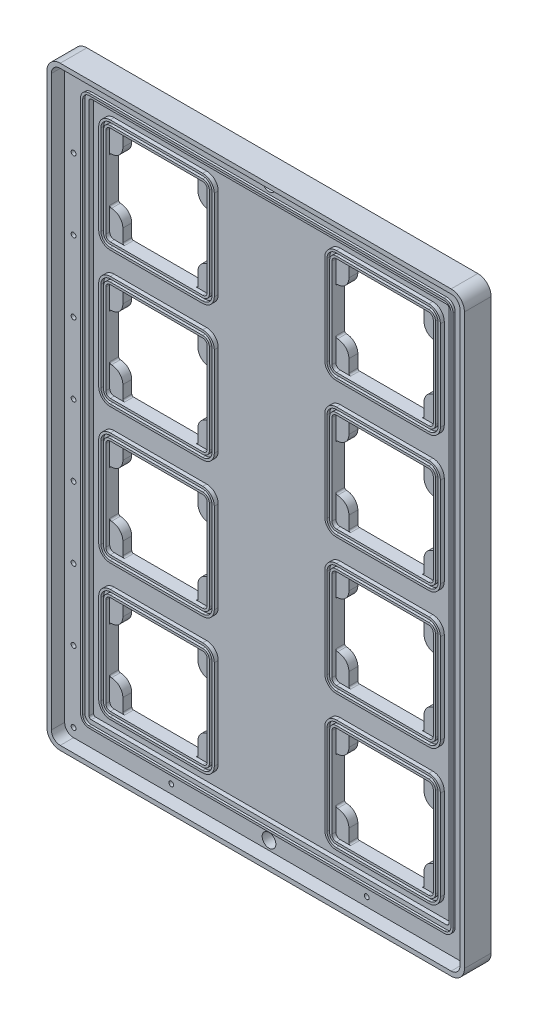
SolidWorks part; units mm, degrees
ref_plane "Front Plane" through (0, 0, 0) normal (0, 0, 1) x (1, 0, 0)
ref_plane "Top Plane" through (0, 0, 0) normal (0, 1, 0) x (1, 0, 0)
ref_plane "Right Plane" through (0, 0, 0) normal (1, 0, 0) x (0, 0, -1)
sketch "Sketch1" plane through (0, 0, 0) normal (0, 0, 1) x (1, 0, 0)
  line L1 (0, 0) -> (292.1, 0)
  line L2 (0, 0) -> (0, 419.1)
  line L3 (0, 419.1) -> (292.1, 419.1)
  line L4 (292.1, 0) -> (292.1, 419.1)
  dimension "D1" = 419.1
  dimension "D2" = 292.1
extrude "Boss-Extrude1" add sketch "Sketch1" along normal blind 9.525
sketch "Sketch4" plane through (0, 0, 9.525) normal (0, 0, 1) x (1, 0, 0)
  line L3 (0, 419.1) -> (0, 0) construction
  line L4 (6.35, 412.75) -> (285.75, 412.75) construction
  line L5 (6.35, 412.75) -> (6.35, 6.35) construction
  line L6 (6.35, 6.35) -> (285.75, 6.35) construction
  line L7 (285.75, 412.75) -> (285.75, 6.35) construction
  line L8 (292.1, 419.1) -> (0, 419.1) construction
  line L9 (292.1, 0) -> (292.1, 419.1) construction
  line L10 (0, 0) -> (292.1, 0) construction
  circle A0 centre (6.35, 6.35) radius 1.7272
  circle A1 centre (6.35, 412.75) radius 1.7272
  circle A2 centre (285.75, 412.75) radius 1.7272
  circle A3 centre (285.75, 6.35) radius 1.7272
  dimension "D5" = 3.4544
  dimension "D1" = 6.35
  dimension "D2" = 6.35
  dimension "D3" = 6.35
  dimension "D4" = 6.35
extrude "Cut-Extrude1" cut sketch "Sketch4" against normal blind 6.985
pattern_linear "LPattern2" count 8 spacing 50.8 along (0, -1, 0) of "Cut-Extrude1"
pattern_linear "LPattern3" count 4 spacing 69.85 along (-1, 0, 0) of "Cut-Extrude1"
sketch "Sketch5" plane through (0, 0, 9.525) normal (0, 0, 1) x (1, 0, 0)
  line L0 (0, 419.1) -> (0, 0) construction
  line L1 (19.05, 406.4) -> (273.05, 406.4) construction
  line L2 (12.7, 400.05) -> (12.7, 19.05) construction
  line L3 (19.05, 12.7) -> (273.05, 12.7) construction
  line L4 (279.4, 400.05) -> (279.4, 19.05) construction
  line L5 (292.1, 419.1) -> (0, 419.1) construction
  line L6 (292.1, 0) -> (292.1, 419.1) construction
  line L7 (0, 0) -> (292.1, 0) construction
  line L8 (19.05, 14.732) -> (273.05, 14.732) construction
  line L9 (14.732, 400.05) -> (14.732, 19.05) construction
  line L10 (19.05, 404.368) -> (273.05, 404.368) construction
  line L11 (277.368, 400.05) -> (277.368, 19.05) construction
  line L12 (12.954, 400.05) -> (12.954, 19.05)
  line L13 (19.05, 406.146) -> (273.05, 406.146)
  line L14 (279.146, 400.05) -> (279.146, 19.05)
  line L15 (19.05, 12.954) -> (273.05, 12.954)
  line L16 (277.622, 400.05) -> (277.622, 19.05)
  line L17 (19.05, 404.622) -> (273.05, 404.622)
  line L18 (14.478, 400.05) -> (14.478, 19.05)
  line L19 (19.05, 14.478) -> (273.05, 14.478)
  arc A0 (273.05, 12.7) -> (279.4, 19.05) centre (273.05, 19.05) ccw construction
  arc A1 (12.7, 19.05) -> (19.05, 12.7) centre (19.05, 19.05) ccw construction
  arc A2 (273.05, 406.4) -> (279.4, 400.05) centre (273.05, 400.05) cw construction
  arc A3 (19.05, 406.4) -> (12.7, 400.05) centre (19.05, 400.05) ccw construction
  arc A4 (14.732, 19.05) -> (19.05, 14.732) centre (19.05, 19.05) ccw construction
  arc A5 (19.05, 404.368) -> (14.732, 400.05) centre (19.05, 400.05) ccw construction
  arc A6 (273.05, 404.368) -> (277.368, 400.05) centre (273.05, 400.05) cw construction
  arc A7 (273.05, 14.732) -> (277.368, 19.05) centre (273.05, 19.05) ccw construction
  arc A8 (19.05, 406.146) -> (12.954, 400.05) centre (19.05, 400.05) ccw
  arc A9 (273.05, 406.146) -> (279.146, 400.05) centre (273.05, 400.05) cw
  arc A10 (273.05, 12.954) -> (279.146, 19.05) centre (273.05, 19.05) ccw
  arc A11 (12.954, 19.05) -> (19.05, 12.954) centre (19.05, 19.05) ccw
  arc A12 (273.05, 404.622) -> (277.622, 400.05) centre (273.05, 400.05) cw
  arc A13 (19.05, 404.622) -> (14.478, 400.05) centre (19.05, 400.05) ccw
  arc A14 (14.478, 19.05) -> (19.05, 14.478) centre (19.05, 19.05) ccw
  arc A15 (273.05, 14.478) -> (277.622, 19.05) centre (273.05, 19.05) ccw
  dimension "D5" = 6.35
  dimension "D1" = 12.7
  dimension "D2" = 12.7
  dimension "D3" = 12.7
  dimension "D4" = 12.7
  dimension "D6" = 2.032
  dimension "D7" = 2.032
  dimension "D8" = 0.254
  dimension "D9" = 0.254
  dimension "D10" = 0.254
sketch "Sketch6" plane through (0, 0, 9.525) normal (0, 0, 1) x (1, 0, 0)
  line L0 (292.1, 419.1) -> (0, 419.1) construction
  line L1 (0, 419.1) -> (0, 0) construction
  line L24 (273.05, 401.6375) -> (19.05, 401.6375)
  line L25 (274.6375, 19.05) -> (274.6375, 400.05)
  line L26 (19.05, 17.4625) -> (273.05, 17.4625)
  line L27 (17.4625, 400.05) -> (17.4625, 19.05)
  line L28 (273.05, 401.6375) -> (19.05, 401.6375)
  line L29 (274.6375, 19.05) -> (274.6375, 400.05)
  line L30 (19.05, 17.4625) -> (273.05, 17.4625)
  line L31 (17.4625, 400.05) -> (17.4625, 19.05)
  arc A20 (19.05, 401.6375) -> (17.4625, 400.05) centre (19.05, 400.05) ccw
  arc A21 (274.6375, 400.05) -> (273.05, 401.6375) centre (273.05, 400.05) ccw
  arc A22 (273.05, 17.4625) -> (274.6375, 19.05) centre (273.05, 19.05) ccw
  arc A23 (17.4625, 19.05) -> (19.05, 17.4625) centre (19.05, 19.05) ccw
  arc A24 (19.05, 401.6375) -> (17.4625, 400.05) centre (19.05, 400.05) ccw
  arc A25 (274.6375, 400.05) -> (273.05, 401.6375) centre (273.05, 400.05) ccw
  arc A26 (273.05, 17.4625) -> (274.6375, 19.05) centre (273.05, 19.05) ccw
  arc A27 (17.4625, 19.05) -> (19.05, 17.4625) centre (19.05, 19.05) ccw
  dimension "D2" = 17.4625
  dimension "D3" = 17.4625
  dimension "D1" = 2.7305
extrude "Cut-Extrude3" cut sketch "Sketch6" against normal blind 3.175
extrude "Boss-Extrude2" add sketch "Sketch5" along normal blind 1.5875 contours L12 A11 L15 A10 L14 A9 L13 A8 A15 L19 A14 L18 A13 L17 A12 L16 region at (15.0752, 404.0248, 9.525)
sketch "Sketch7" plane through (0, 0, 9.525) normal (0, 0, 1) x (1, 0, 0)
  circle A0 centre (146.05, 6.35) radius 4.9022
  circle A1 centre (146.05, 412.75) radius 4.9022
  dimension "D1" = 9.8044
extrude "Cut-Extrude4" cut sketch "Sketch7" against normal through all
fillet "Fillet1" radius 6.35 4 edges at (0, 419.1, 4.7625) (292.1, 419.1, 4.7625) (0, 0, 4.7625) (292.1, 0, 4.7625)
sketch "Sketch8" plane through (0, 0, 0) normal (0, 0, -1) x (-1, 0, 0)
  line L0 (-264.668, 370.459) -> (-264.668, 339.2678)
  line L1 (-255.27, 329.8698) -> (-255.27, 320.8782)
  line L2 (-252.4506, 318.0588) -> (-201.2442, 318.0588)
  line L3 (-198.4248, 320.8782) -> (-198.4248, 329.8698)
  line L4 (-189.0268, 339.2678) -> (-189.0268, 370.459)
  line L5 (-198.4248, 379.857) -> (-198.4248, 388.8486)
  line L6 (-201.2442, 391.668) -> (-252.4506, 391.668)
  line L7 (-255.27, 388.8486) -> (-255.27, 379.857)
  line L8 (-261.8486, 391.668) -> (-261.8486, 318.0588) construction
  line L9 (-264.668, 388.8486) -> (-189.0268, 388.8486) construction
  line L10 (-264.668, 391.668) -> (-189.0268, 391.668) construction
  line L11 (-264.668, 391.668) -> (-264.668, 318.0588) construction
  line L12 (-264.668, 318.0588) -> (-189.0268, 318.0588) construction
  line L13 (-189.0268, 391.668) -> (-189.0268, 318.0588) construction
  line L14 (-264.668, 379.857) -> (-189.0268, 379.857) construction
  line L15 (-264.668, 370.459) -> (-189.0268, 370.459) construction
  line L16 (-264.668, 339.2678) -> (-189.0268, 339.2678) construction
  line L17 (-264.668, 329.8698) -> (-189.0268, 329.8698) construction
  line L18 (-264.668, 320.8782) -> (-189.0268, 320.8782) construction
  line L19 (-255.27, 318.0588) -> (-255.27, 391.668) construction
  line L20 (-252.4506, 391.668) -> (-252.4506, 318.0588) construction
  line L21 (-201.2442, 391.668) -> (-201.2442, 318.0588) construction
  line L22 (-198.4248, 391.668) -> (-198.4248, 318.0588) construction
  line L23 (-191.8462, 318.0588) -> (-191.8462, 391.668) construction
  line L24 (-189.0268, 373.2784) -> (-264.668, 373.2784) construction
  line L27 (-201.2442, 393.7) -> (-252.4506, 393.7)
  line L28 (-257.302, 388.8486) -> (-257.302, 379.857)
  line L29 (-266.7, 370.459) -> (-266.7, 339.2678)
  line L30 (-257.302, 329.8698) -> (-257.302, 320.8782)
  line L31 (-252.4506, 316.0268) -> (-201.2442, 316.0268)
  line L32 (-196.3928, 320.8782) -> (-196.3928, 329.8698)
  line L33 (-186.9948, 339.2678) -> (-186.9948, 370.459)
  line L34 (-196.3928, 379.857) -> (-196.3928, 388.8486)
  line L35 (-285.75, 419.1) -> (-6.35, 419.1) construction
  line L36 (-292.1, 6.35) -> (-292.1, 412.75) construction
  arc A0 (-261.8486, 373.2784) -> (-255.27, 379.857) centre (-261.8486, 379.857) ccw
  arc A1 (-261.8486, 373.2784) -> (-264.668, 370.459) centre (-261.8486, 370.459) ccw
  arc A2 (-264.668, 339.2678) -> (-261.8486, 336.4484) centre (-261.8486, 339.2678) ccw
  arc A3 (-255.27, 329.8698) -> (-261.8486, 336.4484) centre (-261.8486, 329.8698) ccw
  arc A4 (-255.27, 320.8782) -> (-252.4506, 318.0588) centre (-252.4506, 320.8782) ccw
  arc A5 (-201.2442, 318.0588) -> (-198.4248, 320.8782) centre (-201.2442, 320.8782) ccw
  arc A6 (-191.8462, 336.4484) -> (-198.4248, 329.8698) centre (-191.8462, 329.8698) ccw
  arc A7 (-191.8462, 336.4484) -> (-189.0268, 339.2678) centre (-191.8462, 339.2678) ccw
  arc A8 (-189.0268, 370.459) -> (-191.8462, 373.2784) centre (-191.8462, 370.459) ccw
  arc A9 (-198.4248, 379.857) -> (-191.8462, 373.2784) centre (-191.8462, 379.857) ccw
  arc A10 (-198.4248, 388.8486) -> (-201.2442, 391.668) centre (-201.2442, 388.8486) ccw
  arc A11 (-252.4506, 391.668) -> (-255.27, 388.8486) centre (-252.4506, 388.8486) ccw
  arc A12 (-252.4506, 393.7) -> (-257.302, 388.8486) centre (-252.4506, 388.8486) ccw
  arc A13 (-261.8486, 375.3104) -> (-257.302, 379.857) centre (-261.8486, 379.857) ccw
  arc A14 (-261.8486, 375.3104) -> (-266.7, 370.459) centre (-261.8486, 370.459) ccw
  arc A15 (-266.7, 339.2678) -> (-261.8486, 334.4164) centre (-261.8486, 339.2678) ccw
  arc A16 (-257.302, 329.8698) -> (-261.8486, 334.4164) centre (-261.8486, 329.8698) ccw
  arc A17 (-257.302, 320.8782) -> (-252.4506, 316.0268) centre (-252.4506, 320.8782) ccw
  arc A18 (-201.2442, 316.0268) -> (-196.3928, 320.8782) centre (-201.2442, 320.8782) ccw
  arc A19 (-191.8462, 334.4164) -> (-196.3928, 329.8698) centre (-191.8462, 329.8698) ccw
  arc A20 (-191.8462, 334.4164) -> (-186.9948, 339.2678) centre (-191.8462, 339.2678) ccw
  arc A21 (-186.9948, 370.459) -> (-191.8462, 375.3104) centre (-191.8462, 370.459) ccw
  arc A22 (-196.3928, 379.857) -> (-191.8462, 375.3104) centre (-191.8462, 379.857) ccw
  arc A23 (-196.3928, 388.8486) -> (-201.2442, 393.7) centre (-201.2442, 388.8486) ccw
  dimension "D4" = 11.811
  dimension "D5" = 21.209
  dimension "D6" = 52.4002
  dimension "D1" = 73.6092
  dimension "D2" = 75.6412
  dimension "D3" = 2.8194
  dimension "D7" = 61.7982
  dimension "D8" = 70.7898
  dimension "D9" = 2.8194
  dimension "D10" = 9.398
  dimension "D11" = 12.2174
  dimension "D12" = 63.4238
  dimension "D13" = 66.2432
  dimension "D14" = 72.8218
  dimension "D15" = 55.2196
  dimension "D16" = 25.4
  dimension "D17" = 25.4
  dimension "D18" = 2.032
extrude "Cut-Extrude5" cut sketch "Sketch8" against normal blind 3.175
sketch "Sketch10" plane through (0, 0, 0) normal (0, 0, -1) x (-1, 0, 0)
  line L18 (-263.0805, 370.459) -> (-263.0805, 339.2678)
  line L19 (-253.6825, 329.8698) -> (-253.6825, 320.8782)
  line L20 (-252.4506, 319.6463) -> (-201.2442, 319.6463)
  line L21 (-200.0123, 320.8782) -> (-200.0123, 329.8698)
  line L22 (-190.6143, 339.2678) -> (-190.6143, 370.459)
  line L23 (-200.0123, 379.857) -> (-200.0123, 388.8486)
  line L24 (-201.2442, 390.0805) -> (-252.4506, 390.0805)
  line L25 (-253.6825, 388.8486) -> (-253.6825, 379.857)
  line L26 (-263.0805, 370.459) -> (-263.0805, 339.2678)
  line L27 (-253.6825, 329.8698) -> (-253.6825, 320.8782)
  line L28 (-252.4506, 319.6463) -> (-201.2442, 319.6463)
  line L29 (-200.0123, 320.8782) -> (-200.0123, 329.8698)
  line L30 (-190.6143, 339.2678) -> (-190.6143, 370.459)
  line L31 (-200.0123, 379.857) -> (-200.0123, 388.8486)
  line L32 (-201.2442, 390.0805) -> (-252.4506, 390.0805)
  line L33 (-253.6825, 388.8486) -> (-253.6825, 379.857)
  arc A28 (-261.8486, 371.6909) -> (-263.0805, 370.459) centre (-261.8486, 370.459) ccw
  arc A29 (-263.0805, 339.2678) -> (-261.8486, 338.0359) centre (-261.8486, 339.2678) ccw
  arc A30 (-253.6825, 329.8698) -> (-261.8486, 338.0359) centre (-261.8486, 329.8698) ccw
  arc A31 (-253.6825, 320.8782) -> (-252.4506, 319.6463) centre (-252.4506, 320.8782) ccw
  arc A32 (-201.2442, 319.6463) -> (-200.0123, 320.8782) centre (-201.2442, 320.8782) ccw
  arc A33 (-191.8462, 338.0359) -> (-200.0123, 329.8698) centre (-191.8462, 329.8698) ccw
  arc A34 (-191.8462, 338.0359) -> (-190.6143, 339.2678) centre (-191.8462, 339.2678) ccw
  arc A35 (-190.6143, 370.459) -> (-191.8462, 371.6909) centre (-191.8462, 370.459) ccw
  arc A36 (-200.0123, 379.857) -> (-191.8462, 371.6909) centre (-191.8462, 379.857) ccw
  arc A37 (-200.0123, 388.8486) -> (-201.2442, 390.0805) centre (-201.2442, 388.8486) ccw
  arc A38 (-252.4506, 390.0805) -> (-253.6825, 388.8486) centre (-252.4506, 388.8486) ccw
  arc A39 (-261.8486, 371.6909) -> (-253.6825, 379.857) centre (-261.8486, 379.857) ccw
  arc A40 (-261.8486, 371.6909) -> (-263.0805, 370.459) centre (-261.8486, 370.459) ccw
  arc A41 (-263.0805, 339.2678) -> (-261.8486, 338.0359) centre (-261.8486, 339.2678) ccw
  arc A42 (-253.6825, 329.8698) -> (-261.8486, 338.0359) centre (-261.8486, 329.8698) ccw
  arc A43 (-253.6825, 320.8782) -> (-252.4506, 319.6463) centre (-252.4506, 320.8782) ccw
  arc A44 (-201.2442, 319.6463) -> (-200.0123, 320.8782) centre (-201.2442, 320.8782) ccw
  arc A45 (-191.8462, 338.0359) -> (-200.0123, 329.8698) centre (-191.8462, 329.8698) ccw
  arc A46 (-191.8462, 338.0359) -> (-190.6143, 339.2678) centre (-191.8462, 339.2678) ccw
  arc A47 (-190.6143, 370.459) -> (-191.8462, 371.6909) centre (-191.8462, 370.459) ccw
  arc A48 (-200.0123, 379.857) -> (-191.8462, 371.6909) centre (-191.8462, 379.857) ccw
  arc A49 (-200.0123, 388.8486) -> (-201.2442, 390.0805) centre (-201.2442, 388.8486) ccw
  arc A50 (-252.4506, 390.0805) -> (-253.6825, 388.8486) centre (-252.4506, 388.8486) ccw
  arc A51 (-261.8486, 371.6909) -> (-253.6825, 379.857) centre (-261.8486, 379.857) ccw
  dimension "D1" = 1.5875
extrude "Cut-Extrude6" cut sketch "Sketch10" against normal through all
sketch "Sketch11" plane through (0, 0, 0) normal (0, 0, -1) x (-1, 0, 0)
  line L0 (-226.8474, 388.8994) -> (-226.8474, 393.7) construction
  line L1 (-261.8486, 388.8994) -> (-191.8462, 388.8994) construction
  line L2 (-261.8486, 388.8994) -> (-261.8486, 320.8274) construction
  line L3 (-261.8486, 320.8274) -> (-191.8462, 320.8274) construction
  line L4 (-191.8462, 388.8994) -> (-191.8462, 320.8274) construction
  line L5 (-201.2442, 393.7) -> (-252.4506, 393.7) construction
  line L6 (-226.8474, 320.8274) -> (-226.8474, 316.0268) construction
  line L7 (-252.4506, 316.0268) -> (-201.2442, 316.0268) construction
  line L8 (-261.8486, 354.8634) -> (-266.7, 354.8634) construction
  line L9 (-266.7, 370.459) -> (-266.7, 339.2678) construction
  line L10 (-191.8462, 354.8634) -> (-186.9948, 354.8634) construction
  line L11 (-186.9948, 339.2678) -> (-186.9948, 370.459) construction
  circle A0 centre (-261.8486, 388.8994) radius 1.1303
  circle A1 centre (-191.8462, 388.8994) radius 1.1303
  circle A2 centre (-191.8462, 320.8274) radius 1.1303
  circle A3 centre (-261.8486, 320.8274) radius 1.1303
  dimension "D3" = 2.2606
  dimension "D1" = 70.0024
  dimension "D2" = 68.072
extrude "Cut-Extrude7" cut sketch "Sketch11" against normal blind 3.9688
sketch "Sketch12" plane through (0, 0, 6.35) normal (0, 0, 1) x (1, 0, 0)
  line L0 (252.4506, 390.0805) -> (201.2442, 390.0805) construction
  line L1 (193.7893, 390.0805) -> (259.9055, 390.0805)
  line L2 (190.6143, 386.9055) -> (190.6143, 322.8213)
  line L3 (193.7893, 319.6463) -> (259.9055, 319.6463)
  line L4 (263.0805, 386.9055) -> (263.0805, 322.8213)
  line L5 (263.0805, 339.2678) -> (263.0805, 370.459) construction
  line L10 (193.7893, 391.668) -> (259.9055, 391.668)
  line L11 (264.668, 386.9055) -> (264.668, 322.8213)
  line L12 (193.7893, 318.0588) -> (259.9055, 318.0588)
  line L13 (189.0268, 386.9055) -> (189.0268, 322.8213)
  line L14 (187.1218, 386.9055) -> (187.1218, 322.8213)
  line L15 (193.7893, 316.1538) -> (259.9055, 316.1538)
  line L16 (266.573, 386.9055) -> (266.573, 322.8213)
  line L17 (193.7893, 393.573) -> (259.9055, 393.573)
  line L18 (185.5343, 386.9055) -> (185.5343, 322.8213)
  line L19 (193.7893, 314.5663) -> (259.9055, 314.5663)
  line L20 (268.1605, 386.9055) -> (268.1605, 322.8213)
  line L21 (193.7893, 395.1605) -> (259.9055, 395.1605)
  line L22 (201.2442, 319.6463) -> (252.4506, 319.6463) construction
  line L23 (190.6143, 370.459) -> (190.6143, 339.2678) construction
  arc A0 (259.9055, 319.6463) -> (263.0805, 322.8213) centre (259.9055, 322.8213) ccw
  arc A1 (190.6143, 322.8213) -> (193.7893, 319.6463) centre (193.7893, 322.8213) ccw
  arc A2 (259.9055, 390.0805) -> (263.0805, 386.9055) centre (259.9055, 386.9055) cw
  arc A3 (193.7893, 390.0805) -> (190.6143, 386.9055) centre (193.7893, 386.9055) ccw
  arc A4 (259.9055, 391.668) -> (264.668, 386.9055) centre (259.9055, 386.9055) cw
  arc A5 (259.9055, 318.0588) -> (264.668, 322.8213) centre (259.9055, 322.8213) ccw
  arc A6 (189.0268, 322.8213) -> (193.7893, 318.0588) centre (193.7893, 322.8213) ccw
  arc A7 (193.7893, 391.668) -> (189.0268, 386.9055) centre (193.7893, 386.9055) ccw
  arc A8 (187.1218, 322.8213) -> (193.7893, 316.1538) centre (193.7893, 322.8213) ccw
  arc A9 (259.9055, 316.1538) -> (266.573, 322.8213) centre (259.9055, 322.8213) ccw
  arc A10 (259.9055, 393.573) -> (266.573, 386.9055) centre (259.9055, 386.9055) cw
  arc A11 (193.7893, 393.573) -> (187.1218, 386.9055) centre (193.7893, 386.9055) ccw
  arc A12 (185.5343, 322.8213) -> (193.7893, 314.5663) centre (193.7893, 322.8213) ccw
  arc A13 (259.9055, 314.5663) -> (268.1605, 322.8213) centre (259.9055, 322.8213) ccw
  arc A14 (259.9055, 395.1605) -> (268.1605, 386.9055) centre (259.9055, 386.9055) cw
  arc A15 (193.7893, 395.1605) -> (185.5343, 386.9055) centre (193.7893, 386.9055) ccw
  dimension "D1" = 3.175
  dimension "D2" = 1.5875
  dimension "D3" = 1.905
  dimension "D4" = 1.5875
extrude "Boss-Extrude3" add sketch "Sketch12" along normal blind 2.794 contours L21 A15 L18 A12 L19 A13 L20 A14 A11 L17 A10 L16 A9 L15 A8 L14 | L10 A7 L13 A6 L12 A5 L11 A4 A3 L1 A2 L4 A0 L3 A1 L2 region at (226.8474, 390.6125, 6.35) region at (188.7683, 391.9265, 6.35)
extrude "Boss-Extrude4" add sketch "Sketch12<3>" along normal blind 0.7937 contours L17 A11 L14 A8 L15 A9 L16 A10 A7 L10 A4 L11 A5 L12 A6 L13 region at (189.8591, 390.8357, 6.35)
sketch "Sketch12<3>" plane through (0, 0, 6.35) normal (0, 0, 1) x (1, 0, 0) same geometry as "Sketch12"
pattern_linear "LPattern1" count 2 spacing 161.5948 along (-1, 0, 0) count 4 spacing 96.8756 along (0, -1, 0) of "Cut-Extrude6", "Cut-Extrude5", "Cut-Extrude7", "Boss-Extrude3", "Boss-Extrude4"
sketch "Sketch13" plane through (0, 0, 0) normal (0, 0, -1) x (-1, 0, 0)
  line L4 (-6.35, 419.1) -> (-285.75, 419.1)
  line L5 (-292.1, 412.75) -> (-292.1, 6.35)
  line L6 (-285.75, 0) -> (-6.35, 0)
  line L7 (0, 6.35) -> (0, 412.75)
  line L8 (-285.75, -3.175) -> (-6.35, -3.175)
  line L9 (3.175, 6.35) -> (3.175, 412.75)
  line L10 (-6.35, 422.275) -> (-285.75, 422.275)
  line L11 (-295.275, 412.75) -> (-295.275, 6.35)
  line L12 (-285.75, -3.175) -> (-6.35, -3.175)
  line L13 (3.175, 6.35) -> (3.175, 412.75)
  line L14 (-6.35, 422.275) -> (-285.75, 422.275)
  line L15 (-295.275, 412.75) -> (-295.275, 6.35)
  arc A4 (-285.75, 419.1) -> (-292.1, 412.75) centre (-285.75, 412.75) ccw
  arc A5 (-292.1, 6.35) -> (-285.75, 0) centre (-285.75, 6.35) ccw
  arc A6 (-6.35, 0) -> (0, 6.35) centre (-6.35, 6.35) ccw
  arc A7 (0, 412.75) -> (-6.35, 419.1) centre (-6.35, 412.75) ccw
  arc A8 (-295.275, 6.35) -> (-285.75, -3.175) centre (-285.75, 6.35) ccw
  arc A9 (-6.35, -3.175) -> (3.175, 6.35) centre (-6.35, 6.35) ccw
  arc A10 (3.175, 412.75) -> (-6.35, 422.275) centre (-6.35, 412.75) ccw
  arc A11 (-285.75, 422.275) -> (-295.275, 412.75) centre (-285.75, 412.75) ccw
  arc A12 (-295.275, 6.35) -> (-285.75, -3.175) centre (-285.75, 6.35) ccw
  arc A13 (-6.35, -3.175) -> (3.175, 6.35) centre (-6.35, 6.35) ccw
  arc A14 (3.175, 412.75) -> (-6.35, 422.275) centre (-6.35, 412.75) ccw
  arc A15 (-285.75, 422.275) -> (-295.275, 412.75) centre (-285.75, 412.75) ccw
  dimension "D1" = 3.175
  dimension "D2" = 3.175
extrude "Boss-Extrude5" add sketch "Sketch13" against normal blind 19.05
